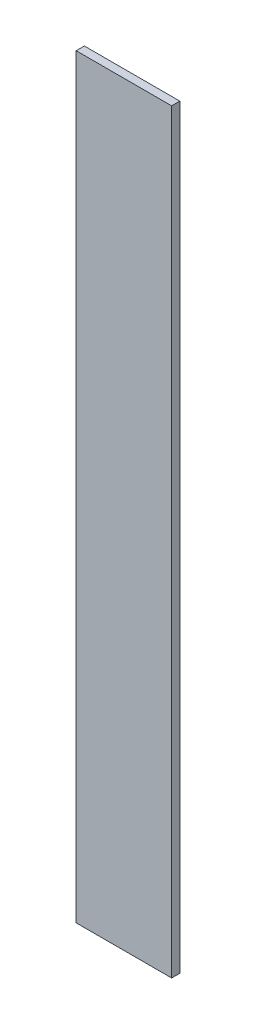
SolidWorks part; units mm, degrees
ref_plane "Front Plane" through (0, 0, 0) normal (0, 0, 1) x (1, 0, 0)
ref_plane "Top Plane" through (0, 0, 0) normal (0, 1, 0) x (1, 0, 0)
ref_plane "Right Plane" through (0, 0, 0) normal (1, 0, 0) x (0, 0, -1)
sketch "Sketch1" plane through (0, 0, 0) normal (0, 0, 1) x (1, 0, 0)
  line L1 (-17.5, 138.5) -> (17.5, 138.5)
  line L2 (-17.5, 138.5) -> (-17.5, -138.5)
  line L3 (-17.5, -138.5) -> (17.5, -138.5)
  line L4 (17.5, 138.5) -> (17.5, -138.5)
  line L5 (-17.5, 138.5) -> (17.5, -138.5) construction
  line L6 (-17.5, -138.5) -> (17.5, 138.5) construction
  point P0 (0, 0)
  dimension "D1" = 35
  dimension "D2" = 277
extrude "Boss-Extrude1" add sketch "Sketch1" along normal blind 3
equation "\"PCLength\"= 320mm'Length across I/O from PS to GPU"
equation "\"PCWidth\"= 242mm'Distance of longest part parallel to GPU(ussually GPU)"
equation "\"PCHeight\"= 172mm'Tallest point with mobo laying flat"
equation "\"WallThickness\"= 9mm'Thickness of each outer tank wall"
equation "\"ThermoBarrierThickness\"= 3mm'Thickness of barrier between hot side and cold side"
equation "\"HotSideGap\"= 35mm'Space in the hot side for a pump"
equation "\"PCClearance\"= 30mm'Clearance from top of tank to top of PC"
equation "\"RadiatorHeight\"= 275mm'Final Height from ground of radiators"
equation "\"AirflowGap\"= 36mm'Distance between radiators and tank for airflow"
equation "\"VolumeSubtraction\"= 230mm"
equation "\"D1@Sketch1\"=\"HotSideGap\""
equation "\"D2@Sketch1\"=\"RadiatorHeight\" + 5 - \"ThermoBarrierThickness\""
equation "\"D1@Boss-Extrude1\"=\"ThermoBarrierThickness\""
